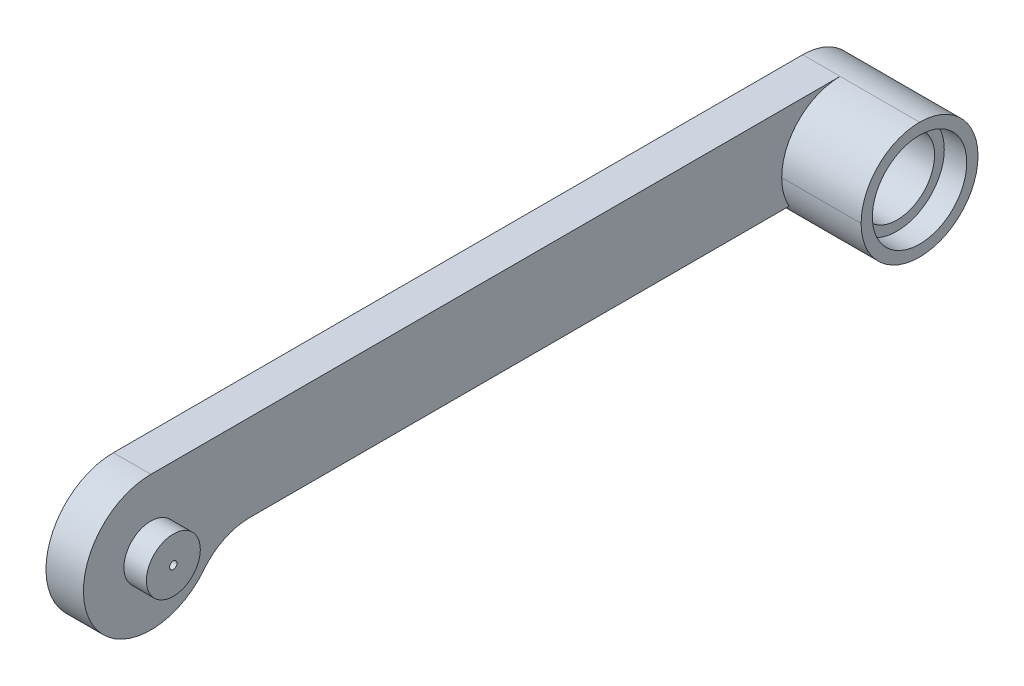
SolidWorks part; units mm, degrees
ref_plane "前视基准面" through (0, 0, 0) normal (0, 0, 1) x (1, 0, 0)
ref_plane "上视基准面" through (0, 0, 0) normal (0, 1, 0) x (1, 0, 0)
ref_plane "右视基准面" through (0, 0, 0) normal (1, 0, 0) x (0, 0, -1)
other "Configuration Table"
sketch "草图1" plane through (0, 0, 0) normal (1, 0, 0) x (0, 0, -1)
  line L0 (46, 3.3) -> (46, -4.5) construction
  line L1 (0, -4.5) -> (49.9, -4.5)
  line L2 (0, -4.5) -> (0, 3.3)
  line L3 (0, 3.3) -> (49.9, 3.3)
  line L4 (49.9, -4.5) -> (49.9, 3.3)
  line L6 (42.1, -4.5) -> (49.9, -4.5)
  line L7 (42.1, -4.5) -> (42.1, 3.3)
  line L8 (42.1, 3.3) -> (49.9, 3.3)
  line L9 (49.9, -4.5) -> (49.9, 3.3)
  line L10 (42.1, -4.5) -> (49.9, 3.3) construction
  line L11 (42.1, 3.3) -> (49.9, -4.5) construction
  circle A4 centre (0, 0) radius 1.8
  circle A5 centre (0, 0) radius 4.5
  circle A6 centre (46, -0.6) radius 2.5
  circle A7 centre (46, -0.6) radius 3.15
  circle A8 centre (0, 0) radius 0.25
  point P9 (46, -0.6)
  dimension "D1" = 3.6
  dimension "D4" = 46
  dimension "D5" = 3.9
  dimension "D2" = 9
  dimension "D6" = 5
  dimension "D7" = 6.3
  dimension "D8" = 0.5
  dimension "D3" = 7.8
extrude "凸台-拉伸1" add sketch "草图1" along normal blind 2.5 contours A5 | L3 L4 L1 L2
extrude "凸台-拉伸3" add sketch "草图1<6>" along normal blind 1.5 from surface contours L2 A4 | L2 A4 region at (0, 0, 0.7769) region at (0, 0, -0.7769) starting at face at (2.5, -0.0392, -24.2851)
sketch "草图1<6>" plane through (0, 0, 0) normal (1, 0, 0) x (0, 0, -1) same geometry as "草图1"
extrude "凸台-拉伸2" add sketch "草图1<5>" along normal blind 7.8 contours A6 | A7 A6 | L7 L1 L4 L3 A7 region at (0, -0.6, -42.2103) region at (0, -0.6, -46) region at (0, -0.6, -42.9391)
sketch "草图1<5>" plane through (0, 0, 0) normal (1, 0, 0) x (0, 0, -1) same geometry as "草图1"
extrude "切除-拉伸1" cut sketch "草图1<7>" along normal through all contours A6 region at (0, -0.6, -46)
sketch "草图1<7>" plane through (0, 0, 0) normal (1, 0, 0) x (0, 0, -1) same geometry as "草图1"
extrude "切除-拉伸2" cut sketch "草图1<8>" along normal blind 1.5 contours A7 A6 region at (0, -0.6, -42.9391)
sketch "草图1<8>" plane through (0, 0, 0) normal (1, 0, 0) x (0, 0, -1) same geometry as "草图1"
extrude "切除-拉伸3" cut sketch "草图1<9>" against normal blind 1.5 from surface contours A7 A6 region at (0, -0.6, -42.9391) starting at face at (7.8, -0.6, -48.5)
sketch "草图1<9>" plane through (0, 0, 0) normal (1, 0, 0) x (0, 0, -1) same geometry as "草图1"
sketch "草图2" plane through (0, 0, 0) normal (-1, 0, 0) x (0, 0, 1)
  line L0 (-3.0594, 3.3) -> (-49.9, 3.3) construction
  line L1 (-42.1, 3.3) -> (-4.5, 3.3)
  line L2 (-42.1, 3.3) -> (-42.1, 1.3)
  line L3 (-42.1, 1.3) -> (-4.5, 1.3)
  line L4 (-4.5, 3.3) -> (-4.5, 1.3)
  line L5 (-42.1, 3.3) -> (-42.1, -4.5) construction
  line L6 (-4.5, 3.3) -> (-3.0594, 3.3)
  line L8 (-4.5, 1.3) -> (-4.3081, 1.3)
  line L9 (-4.5, 1.3) -> (-4.5, 3.3)
  line L10 (-4.5, 3.3) -> (-4.3081, 3.3)
  line L11 (-4.3081, 1.3) -> (-4.3081, 3.3)
  arc A1 (0, -4.5) -> (-3.0594, 3.3) centre (0, 0) ccw construction
  circle A2 centre (0, 0) radius 4.5
  line M7 (-3.0594, 3.3) -> (-49.9, 3.3)
  dimension "D1" = 2
extrude "切除-拉伸4" cut sketch "草图2" against normal through all contours A2 L11 M7 | L8 L11 L6 L4 | L4 L2 L3 M7 region at (0, 2.3, -23.3) region at (0, 2.3, -4.4041) region at (0, 2.7076, -3.9302)
fillet "圆角1" radius 3.9 5 edges at (3.9, -4.5, -49.9) (3.9, 3.3, -49.9) (5.15, -4.5, -42.1) (3.9, 3.3, -42.1) (1.25, 1.3, -4.3081)
ref_plane "基准面1" through (0, -10, 0) normal (0, 1, 0) x (1, 0, 0)
mirror "镜向2" about plane through (0, -10, 0) normal (0, 1, 0) of bodies 118 114
sketch "草图3" plane through (2.5, 0, 0) normal (1, 0, 0) x (0, 0, -1)
  line L1 (-11.0856, 14.9816) -> (53.6185, 14.9816)
  line L2 (-11.0856, 14.9816) -> (-11.0856, -8.3209)
  line L3 (-11.0856, -8.3209) -> (53.6185, -8.3209)
  line L4 (53.6185, 14.9816) -> (53.6185, -8.3209)
extrude "切除-拉伸5" cut sketch "草图3" against normal through all and the other way through all
